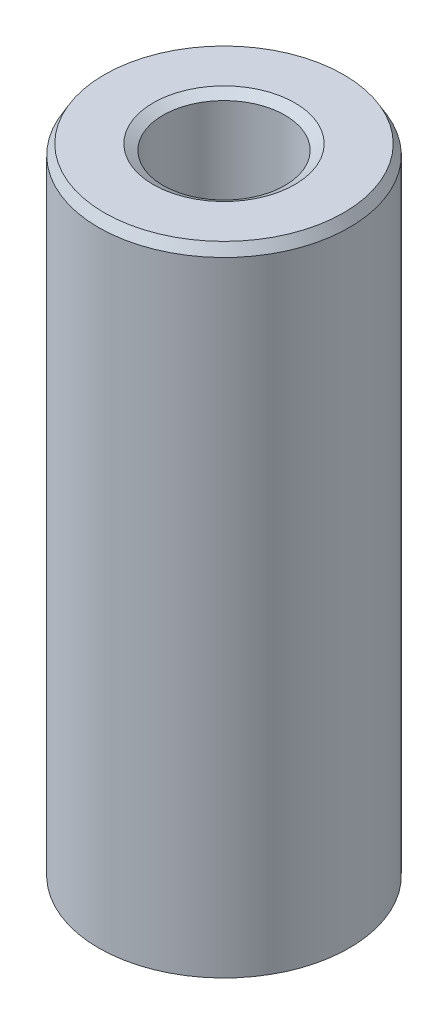
SolidWorks part; units mm, degrees
ref_plane "Front Plane" through (0, 0, 0) normal (0, 0, 1) x (1, 0, 0)
ref_plane "Top Plane" through (0, 0, 0) normal (0, 1, 0) x (1, 0, 0)
ref_plane "Right Plane" through (0, 0, 0) normal (1, 0, 0) x (0, 0, -1)
sketch "Sketch1" plane through (0, 0, 0) normal (0, 1, 0) x (1, 0, 0)
  circle A0 centre (0, 0) radius 17.5
  dimension "SLEEVE_OD" = 35
extrude "Boss-Extrude1" add sketch "Sketch1" along normal blind 89.2718
sketch "Sketch2" plane through (0, 0, 0) normal (0, 1, 0) x (1, 0, 0)
  circle A0 centre (0, 0) radius 8.5065
  dimension "BORE_D" = 17.013
extrude "Cut-Extrude1" cut sketch "Sketch2" along normal through all
chamfer "Chamfer1" distance 1.3833 angle 30 4 edges at (0, 89.2718, 8.5065) (0, 0, 8.5065) (0, 0, 17.5) (0, 89.2718, 17.5) first distance on face at (0, 89.2718, 8.5065) first distance on face at (0, 0, 8.5065) first distance on face at (0, 89.2718, 17.5)
